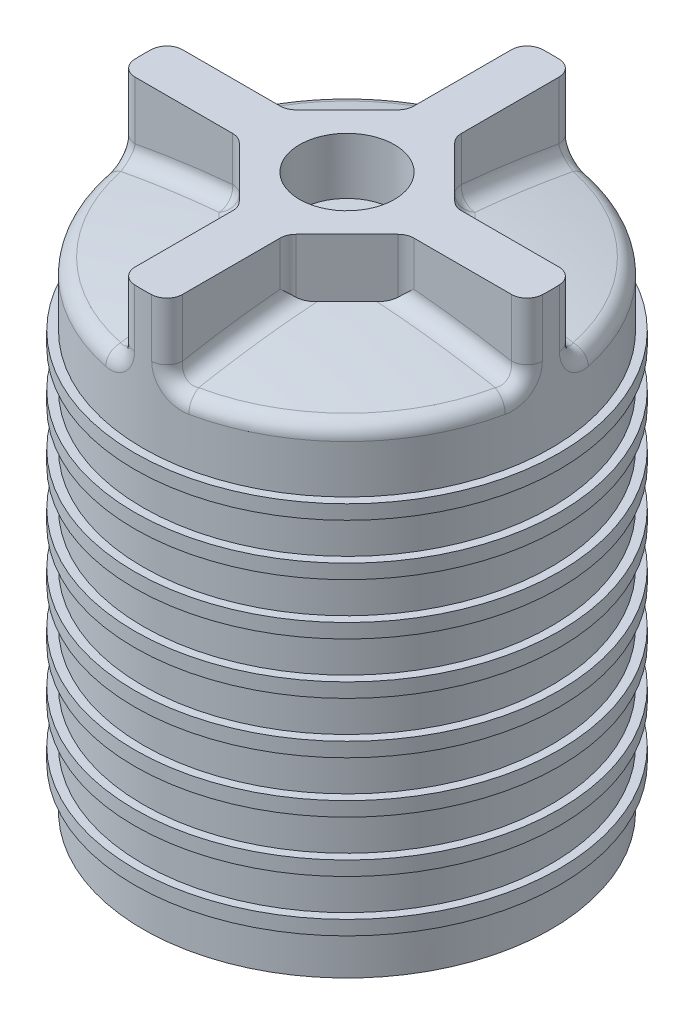
SolidWorks part; units mm, degrees
material "Titanium Ti-5Al-2.5Sn"
ref_plane "Front Plane" through (0, 0, 0) normal (0, 0, 1) x (1, 0, 0)
ref_plane "Top Plane" through (0, 0, 0) normal (0, 1, 0) x (1, 0, 0)
ref_plane "Right Plane" through (0, 0, 0) normal (1, 0, 0) x (0, 0, -1)
sketch "Sketch1" plane through (0, 0, 0) normal (0, 0, 1) x (1, 0, 0)
  line L0 (0, 0) -> (0, 63.0108) construction
  line L2 (-25.7928, 60.3645) -> (-25.7928, 0)
  line L3 (-25.7928, 0) -> (0, 0)
  line L4 (0, 0) -> (0, 63.0108)
  arc A0 (0, 63.0108) -> (-25.7928, 60.3645) centre (0, -64.0109) ccw
revolve "Revolve1" add sketch "Sketch1" angle 360 about L0
ref_plane "Plane1" through (0, 70, 0) normal (0, 1, 0) x (1, 0, 0)
sketch "Sketch7" plane through (0, 70, 0) normal (0, 1, 0) x (1, 0, 0)
  line L0 (25.7928, 0) -> (-25.7928, 0) construction
  line L1 (0, 25.7928) -> (0, -25.7928) construction
  line L18 (3, 25.6178) -> (3, 10.6178)
  line L19 (-3, 25.6178) -> (-3, 10.6178)
  line L20 (-25.6178, 3) -> (-10.6178, 3)
  line L21 (-25.6178, -3) -> (-10.6178, -3)
  line L22 (-3, -25.6178) -> (-3, -10.6178)
  line L23 (3, -25.6178) -> (3, -10.6178)
  line L24 (25.6178, 3) -> (10.6178, 3)
  line L25 (25.6178, -3) -> (10.6178, -3)
  line L26 (3, 10.6178) -> (10.6178, 3)
  line L27 (-3, 10.6178) -> (-10.6178, 3)
  line L28 (-10.6178, -3) -> (-3, -10.6178)
  line L29 (3, -10.6178) -> (10.6178, -3)
  circle A2 centre (0, 0) radius 6
  circle A3 centre (0, 0) radius 25.7928 construction
  arc A4 (-3, 25.6178) -> (3, 25.6178) centre (0, 0) cw
  arc A5 (-25.6178, 3) -> (-25.6178, -3) centre (0, 0) ccw
  arc A6 (3, -25.6178) -> (-3, -25.6178) centre (0, 0) cw
  arc A7 (25.6178, 3) -> (25.6178, -3) centre (0, 0) cw
  dimension "D1" = 12
  dimension "D6" = 25.7928
  dimension "D9" = 25.7928
  dimension "D12" = 25.7928
  dimension "D15" = 25.7928
  dimension "D2" = 3
  dimension "D3" = 3
  dimension "D4" = 15
  dimension "D5" = 15
  dimension "D7" = 3
  dimension "D8" = 3
  dimension "D10" = 15
  dimension "D11" = 15
  dimension "D13" = 15
  dimension "D14" = 15
  dimension "D16" = 15
  dimension "D17" = 15
extrude "Boss-Extrude4" add sketch "Sketch7" against normal up to next
sketch "Sketch11" plane through (0, 0, 0) normal (0, 0, 1) x (1, 0, 0)
  line L0 (-25.7928, 5.3525) -> (-26.8398, 5.3525)
  line L1 (-25.7928, 70) -> (-25.7928, 0) construction
  line L2 (-26.8398, 5.3525) -> (-26.8398, 7.1609)
  line L3 (-26.8398, 7.1609) -> (-25.7928, 7.1609)
  line L4 (-25.7928, 7.1609) -> (-25.7928, 5.3525)
revolve "Revolve2" add sketch "Sketch11" angle 360 about axis through (0, 0, 0) along (0, -1, 0)
pattern_linear "LPattern1" count 8 spacing 6.5 along (0, 1, 0) of "Revolve2"
fillet "Fillet4" radius 2 31 edges at (-18.2383, 60.3645, -18.2383) (18.2383, 60.3645, -18.2383) (-18.2383, 60.3645, 18.2383) (18.2383, 60.3645, 18.2383) (-18.1501, 61.6716, -3) (-10.6178, 66.2654, -3) (-6.8089, 62.6453, -6.8089) (-3, 66.2654, -10.6178) (-3, 61.6716, -18.1501) (-3, 65.1823, -25.6178) (3, 65.1823, -25.6178) (3, 61.6716, -18.1501) (3, 66.2654, -10.6178) (6.8089, 62.6453, -6.8089) (10.6178, 66.2654, -3) (18.1501, 61.6716, -3) (25.6178, 65.1823, -3) (-10.6178, 66.2654, 3) (-3, 66.2654, 10.6178) (-25.6178, 65.1823, -3) (-25.6178, 65.1823, 3) (-18.1501, 61.6716, 3) (-6.8089, 62.6453, 6.8089) (-3, 61.6716, 18.1501) (-3, 65.1823, 25.6178) (18.1501, 61.6716, 3) (25.6178, 65.1823, 3) (3, 65.1823, 25.6178) (3, 61.6716, 18.1501) (3, 66.2654, 10.6178) (10.6178, 66.2654, 3)
